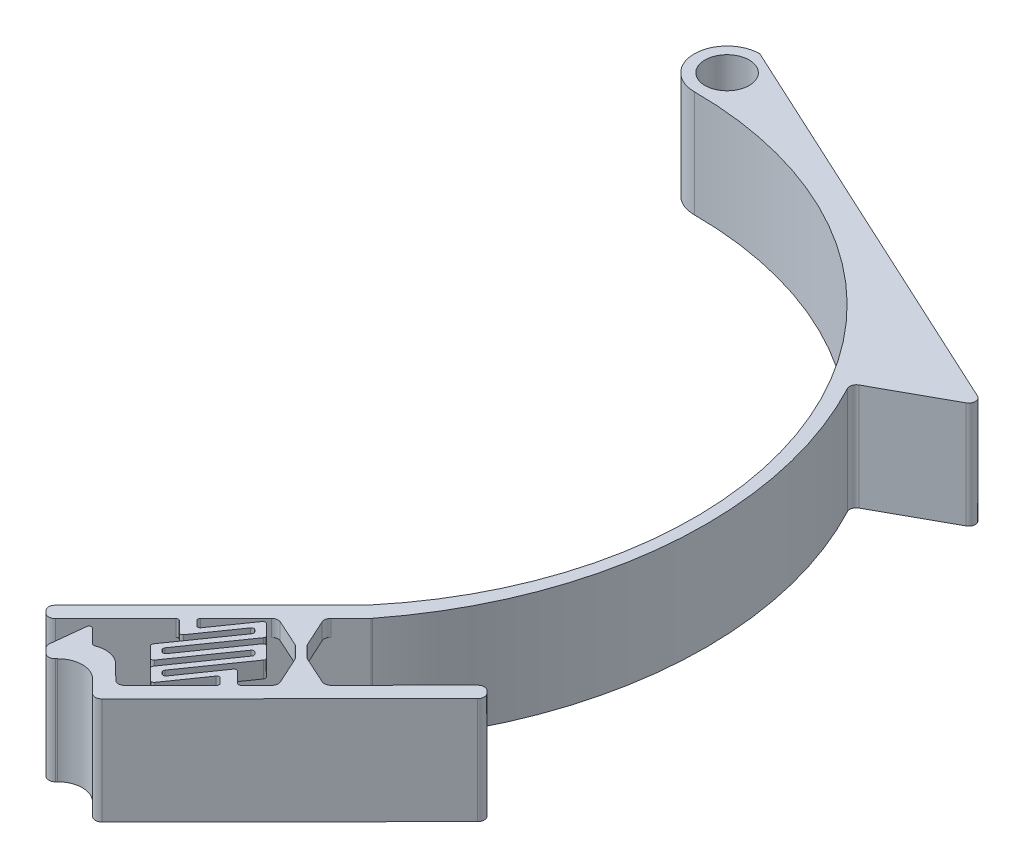
SolidWorks part; units mm, degrees
ref_plane "Front Plane" through (0, 0, 0) normal (0, 0, 1) x (1, 0, 0)
ref_plane "Top Plane" through (0, 0, 0) normal (0, 1, 0) x (1, 0, 0)
ref_plane "Right Plane" through (0, 0, 0) normal (1, 0, 0) x (0, 0, -1)
sketch "Sketch1" plane through (0, 0, 0) normal (0, 1, 0) x (1, 0, 0)
  line L0 (0, 0) -> (34.472, -28.9254) construction
  line L1 (0, 0) -> (0, -45) construction
  line L2 (0, 0) -> (63.5762, -53.3468) construction
  line L3 (0, 53) -> (50.8207, 29.4786)
  line L4 (50.8207, 29.4786) -> (40.3111, 23.6864)
  line L5 (0, 53) -> (0, 49)
  line L7 (0, 49) -> (0, 53)
  line L8 (34.472, -28.9254) -> (20.3504, -43.088)
  line L9 (20.3504, -43.088) -> (21.7666, -44.5002)
  line L10 (21.7666, -44.5002) -> (35.8883, -30.3376)
  line L11 (35.8883, -30.3376) -> (34.472, -28.9254)
  line L12 (30.2642, -52.9732) -> (28.8479, -51.561)
  line L13 (28.8479, -51.561) -> (50.0304, -30.3171)
  line L14 (50.0304, -30.3171) -> (51.4466, -31.7293)
  line L15 (51.4466, -31.7293) -> (30.2642, -52.9732)
  line L17 (24.0046, -45.3195) -> (29.2708, -50.5705)
  line L18 (35.083, -42.2442) -> (29.8168, -36.9932)
  line L19 (29.8168, -36.9932) -> (24.5858, -44.4869)
  line L21 (29.2708, -50.5705) -> (34.5017, -43.0768)
  line L22 (24.0046, -45.3195) -> (24.5858, -44.4869)
  line L24 (24.5858, -44.4869) -> (30.2601, -50.1448) construction
  line L25 (34.5017, -43.0768) -> (28.8274, -37.4189) construction
  line L26 (29.3086, -49.196) -> (33.9584, -42.535)
  line L27 (33.9584, -42.535) -> (33.321, -41.8995)
  line L28 (33.321, -41.8995) -> (28.6713, -48.5606)
  line L29 (28.6713, -48.5606) -> (29.3086, -49.196)
  line L30 (28.1279, -48.0187) -> (27.4906, -47.3833)
  line L31 (27.4906, -47.3833) -> (32.1403, -40.7222)
  line L32 (32.1403, -40.7222) -> (32.7777, -41.3577)
  line L33 (32.7777, -41.3577) -> (28.1279, -48.0187)
  line L34 (26.9472, -46.8415) -> (26.3099, -46.206)
  line L35 (26.3099, -46.206) -> (30.9596, -39.5449)
  line L36 (30.9596, -39.5449) -> (31.597, -40.1804)
  line L37 (31.597, -40.1804) -> (26.9472, -46.8415)
  line L38 (25.7665, -45.6642) -> (25.1292, -45.0287)
  line L39 (25.1292, -45.0287) -> (29.7789, -38.3677)
  line L40 (29.7789, -38.3677) -> (30.4163, -39.0031)
  line L41 (30.4163, -39.0031) -> (25.7665, -45.6642)
  line L42 (34.5017, -43.0768) -> (35.083, -42.2442)
  line L43 (24.5858, -44.4869) -> (25.1292, -45.0287) construction
  line L44 (25.7665, -45.6642) -> (26.3099, -46.206) construction
  line L45 (26.9472, -46.8415) -> (27.4906, -47.3833) construction
  line L46 (28.1279, -48.0187) -> (28.6713, -48.5606) construction
  line L47 (29.3086, -49.196) -> (29.852, -49.7378) construction
  line L48 (30.2396, -36.0026) -> (34.1313, -37.7648)
  line L49 (34.1313, -37.7648) -> (35.5475, -39.1769)
  line L50 (35.5475, -39.1769) -> (37.3209, -43.0635)
  line L51 (37.3209, -43.0635) -> (40.1452, -40.2309)
  line L52 (40.1452, -40.2309) -> (36.2536, -38.4688)
  line L53 (36.2536, -38.4688) -> (34.8373, -37.0566)
  line L54 (34.8373, -37.0566) -> (33.0639, -33.1701)
  line L55 (33.0639, -33.1701) -> (30.2396, -36.0026)
  line L56 (36.0041, -30.211) -> (35.8883, -30.3376)
  line L57 (20.3504, -43.088) -> (21.7666, -44.5002)
  line L58 (20.3504, -43.088) -> (14.7017, -48.7531)
  line L59 (21.7666, -44.5002) -> (16.118, -50.1653)
  line L60 (14.7017, -48.7531) -> (16.118, -50.1653)
  line L61 (16.118, -50.1653) -> (20.3545, -45.9165) construction
  line L62 (16.118, -50.1653) -> (18.9505, -52.9896) construction
  line L63 (20.3545, -45.9165) -> (23.187, -48.7408) construction
  line L64 (18.9505, -52.9896) -> (23.187, -48.7408) construction
  line L69 (30.2642, -52.9732) -> (27.4399, -55.8057)
  line L70 (27.4399, -55.8057) -> (23.1911, -51.5692)
  line L71 (28.8479, -51.561) -> (30.2642, -52.9732)
  line L72 (23.1911, -51.5692) -> (20.3668, -54.4017)
  line L73 (20.3668, -54.4017) -> (18.9505, -52.9896)
  line L74 (18.9505, -52.9896) -> (23.187, -48.7408)
  line L75 (23.187, -48.7408) -> (27.4358, -52.9773)
  line L76 (27.4358, -52.9773) -> (28.8479, -51.561)
  line L77 (28.8479, -51.561) -> (30.2642, -52.9732)
  line L82 (18.9505, -52.9896) -> (21.7748, -50.1571)
  line L83 (21.7748, -50.1571) -> (19.5088, -47.8976)
  line L84 (19.5088, -47.8976) -> (18.9505, -52.9896)
  line L85 (33.6299, -44.3257) -> (34.8496, -45.5419)
  line L86 (34.8496, -45.5419) -> (33.7905, -46.6041)
  line L87 (33.7905, -46.6041) -> (32.7581, -45.5747)
  line L88 (32.7581, -45.5747) -> (33.6299, -44.3257)
  line L89 (24.2379, -42.0218) -> (25.4576, -43.2379)
  line L90 (25.4576, -43.2379) -> (26.3295, -41.989)
  line L91 (26.3295, -41.989) -> (25.297, -40.9596)
  line L92 (25.297, -40.9596) -> (24.2379, -42.0218)
  line L93 (34.8394, -38.4709) -> (46.4509, -26.8257) construction
  line L94 (42.9653, -37.1521) -> (36.0041, -30.211) construction
  circle A0 centre (0, 0) radius 45 construction
  arc A1 (0, 45) -> (34.472, -28.9254) centre (0, 0) cw
  arc A2 (0, 45) -> (0, 53) centre (0, 49) cw
  arc A4 (36.0041, -30.211) -> (0, 49) centre (-2.6664, 0) ccw
  circle A5 centre (0, 49) radius 2.7
  arc A6 (40.3111, 23.6864) -> (0, 49) centre (-2.6664, 0) ccw
  point P72 (33.2743, -46.0894)
  dimension "D1" = 90
  dimension "D5" = 56
  dimension "D6" = 5.4
  dimension "D9" = 2
  dimension "D2" = 50
  dimension "D3" = 8
  dimension "D4" = 2
  dimension "D7" = 12
  dimension "D8" = 2
  dimension "D10" = 1
  dimension "D11" = 10
  dimension "D12" = 10
  dimension "D13" = 0.9
  dimension "D14" = 1
  dimension "D15" = 0.4
  dimension "D16" = 0.4
  dimension "D17" = 10
  dimension "D18" = 1
  dimension "D19" = 4
  dimension "D20" = 4
  dimension "D21" = 1
  dimension "D22" = 20
  dimension "D23" = 30
  dimension "D24" = 2
  dimension "D25" = 4
  dimension "D26" = 0.1716
  dimension "D27" = 4
  dimension "D28" = 8
  dimension "D29" = 4
  dimension "D30" = 2
  dimension "D31" = 2
  dimension "D32" = 2
  dimension "D33" = 3.2
  dimension "D34" = 4
  dimension "D35" = 1.5
  dimension "D36" = 6
  dimension "D37" = 1.5
  dimension "D38" = 6
extrude "Boss-Extrude1" add sketch "Sketch1" along normal blind 13
sketch "Sketch2" plane through (-10.6921, 0, 10.7232) normal (-0.7061, 0, 0.7081) x (0.7081, 0, 0.7061)
  line L1 (46.8344, 11) -> (56.8344, 11)
  line L2 (46.8344, 11) -> (46.8344, 2)
  line L3 (46.8344, 2) -> (56.8344, 2)
  line L4 (56.8344, 11) -> (56.8344, 2)
  line L6 (48.9977, 13) -> (56.4344, 13) construction
  line L7 (46.8344, 13) -> (46.8344, 0) construction
  dimension "D1" = 10
  dimension "D2" = 9
  dimension "D3" = 2
extrude "Cut-Extrude1" cut sketch "Sketch2" against normal through all
fillet "Fillet2" radius 0.8 24 edges at (40.3111, 6.5, -23.6864) (50.8207, 6.5, -29.4786) (37.3209, 12, 43.0635) (35.5475, 12, 39.1769) (34.1313, 12, 37.7648) (30.2396, 12, 36.0026) (33.0639, 12, 33.1701) (40.1452, 1, 40.2309) (40.1452, 12, 40.2309) (34.8373, 1, 37.0566) (36.2536, 1, 38.4688) (34.8373, 12, 37.0566) (36.2536, 12, 38.4688) (50.0304, 6.5, 30.3171) (51.4466, 6.5, 31.7293) (27.4399, 6.5, 55.8057) (27.4358, 6.5, 52.9773) (18.9505, 6.5, 52.9896) (20.3668, 6.5, 54.4017) (16.118, 6.5, 50.1653) (14.7017, 6.5, 48.7531) (30.2396, 1, 36.0026) (33.0639, 1, 33.1701) (37.3209, 1, 43.0635)
fillet "Fillet4" radius 3 1 edges at (23.1911, 6.5, 51.5692)
fillet "Fillet5" radius 3 1 edges at (23.187, 6.5, 48.7408)
fillet "Fillet6" radius 0.3 2 edges at (19.5088, 6.5, 47.8976) (21.7748, 6.5, 50.1571)
sketch "Sketch3" plane through (0, 13, 0) normal (0, 1, 0) x (1, 0, 0)
  line L0 (33.6299, -44.3257) -> (35.083, -42.2442)
  line L1 (35.083, -42.2442) -> (33.9023, -41.0669)
  line L2 (35.083, -42.2442) -> (29.8168, -36.9932) construction
  line L3 (33.9023, -41.0669) -> (32.4492, -43.1484)
  line L4 (33.321, -41.8995) -> (28.6713, -48.5606) construction
  line L5 (32.4492, -43.1484) -> (33.6299, -44.3257)
  line L6 (25.4576, -43.2379) -> (24.0046, -45.3195)
  line L7 (24.0046, -45.3195) -> (25.1853, -46.4968)
  line L8 (24.0046, -45.3195) -> (29.2708, -50.5705) construction
  line L9 (25.1853, -46.4968) -> (26.6383, -44.4152)
  line L10 (30.4163, -39.0031) -> (25.7665, -45.6642) construction
  line L11 (26.6383, -44.4152) -> (25.4576, -43.2379)
  line L12 (30.9596, -39.5449) -> (31.597, -40.1804)
  line L13 (31.597, -40.1804) -> (32.1782, -39.3478)
  line L14 (32.1782, -39.3478) -> (31.5409, -38.7123)
  line L15 (31.5409, -38.7123) -> (30.9596, -39.5449)
  line L16 (30.9596, -39.5449) -> (28.1279, -48.0187)
  line L17 (28.1279, -48.0187) -> (27.4906, -47.3833)
  line L18 (27.4906, -47.3833) -> (26.9094, -48.2159)
  line L19 (26.9094, -48.2159) -> (27.5467, -48.8514)
  line L20 (27.5467, -48.8514) -> (28.1279, -48.0187)
  line L21 (24.2379, -42.0218) -> (25.4576, -43.2379) construction
  line L22 (33.6299, -44.3257) -> (34.8496, -45.5419) construction
  line L23 (26.3099, -46.206) -> (30.9596, -39.5449) construction
  line L24 (32.7777, -41.3577) -> (28.1279, -48.0187) construction
extrude "Cut-Extrude2" cut sketch "Sketch3" against normal through all contours L9 L11 L6 L7 | L19 L20 L17 L18 | L3 L5 L0 L1 | L14 L15 L12 L13
fillet "Fillet7" radius 0.3 48 edges at (29.8168, 1, 36.9932) (31.5409, 1, 38.7123) (33.9023, 1, 41.0669) (33.0865, 1, 43.7839) (34.8496, 1, 45.5419) (32.7581, 1, 45.5747) (33.7905, 1, 46.6041) (32.1782, 1, 39.3478) (32.1403, 1, 40.7222) (32.7777, 1, 41.3577) (29.7789, 1, 38.3677) (30.4163, 1, 39.0031) (26.9094, 1, 48.2159) (27.5467, 1, 48.8514) (29.2708, 1, 50.5705) (28.6713, 1, 48.5606) (29.3086, 1, 49.196) (26.3099, 1, 46.206) (26.9472, 1, 46.8415) (25.1853, 1, 46.4968) (25.297, 1, 40.9596) (26.3295, 1, 41.989) (26.9472, 12, 46.8415) (33.0865, 12, 43.7839) (26.3295, 12, 41.989) (30.4163, 12, 39.0031) (32.7777, 12, 41.3577) (29.8168, 12, 36.9932) (32.1782, 12, 39.3478) (33.7905, 12, 46.6041) (34.8496, 12, 45.5419) (29.3086, 12, 49.196) (28.6713, 12, 48.5606) (25.1853, 12, 46.4968) (26.3099, 12, 46.206) (25.297, 12, 40.9596) (26.001, 1, 43.7798) (24.2379, 1, 42.0218) (24.2379, 12, 42.0218) (26.001, 12, 43.7798) (29.7789, 12, 38.3677) (31.5409, 12, 38.7123) (32.1403, 12, 40.7222) (33.9023, 12, 41.0669) (32.7581, 12, 45.5747) (27.5467, 12, 48.8514) (29.2708, 12, 50.5705) (26.9094, 12, 48.2159)
